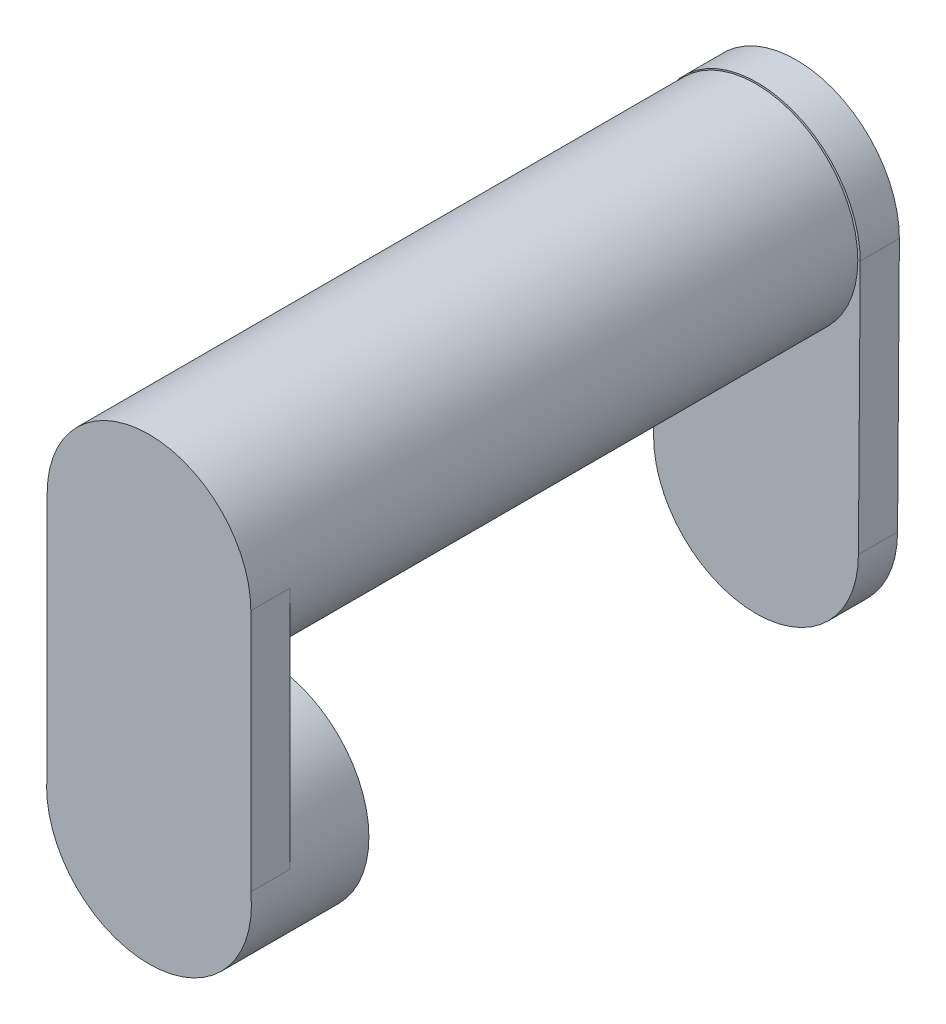
SolidWorks part; units mm, degrees
material "Ti-6Al-2Sn-2Zr-2Mo-2Cr-0.25Si (SS)"
ref_plane "Front Plane" through (0, 0, 0) normal (0, 0, 1) x (1, 0, 0)
ref_plane "Top Plane" through (0, 0, 0) normal (0, 1, 0) x (1, 0, 0)
ref_plane "Right Plane" through (0, 0, 0) normal (1, 0, 0) x (0, 0, -1)
sketch "Sketch1" plane through (0, 0, 0) normal (0, 0, 1) x (1, 0, 0)
  circle A0 centre (0, 0) radius 26.15
  circle A1 centre (0, 0) radius 20.4
  dimension "D1" = 52.3
  dimension "D2" = 40.8
extrude "Boss-Extrude1" add sketch "Sketch1" along normal blind 30 contours A1 | A0
ref_plane "Plane1" through (0, 0, 30) normal (0, 0, 1) x (1, 0, 0)
sketch "Sketch2" plane through (0, 0, 30) normal (0, 0, 1) x (1, 0, 0)
  circle A0 centre (0, 0) radius 26.15
sketch "Sketch10" plane through (0, 0, 30) normal (0, 0, 1) x (1, 0, 0)
  line L0 (-26, 65) -> (-26, 0)
  line L1 (26, 65) -> (26, 0)
  arc A0 (-26, 0) -> (26, 0) centre (0, 0) ccw
  arc A1 (26, 65) -> (-26, 65) centre (0, 65) ccw
  dimension "D1" = 52
  dimension "D2" = 65
extrude "Boss-Extrude7" add sketch "Sketch10" against normal blind 10
ref_plane "Plane5" through (0, 0, 20) normal (0, 0, -1) x (-1, 0, 0)
sketch "Sketch11" plane through (0, 0, 20) normal (0, 0, -1) x (-1, 0, 0)
  circle A0 centre (0, 65) radius 26
extrude "Extrude-Thin1" add sketch "Sketch11" along normal blind 145 thin contours A0 thin type one direction reverse wall 8
ref_plane "Plane6" through (0, 0, -125) normal (0, 0, -1) x (-1, 0, 0)
sketch "Sketch12" plane through (0, 0, -125) normal (0, 0, -1) x (-1, 0, 0)
  line L0 (-26.6135, 65.1347) -> (-26.15, 0)
  line L1 (26, 65) -> (26.15, 0)
  arc A0 (26.0024, 63.9396) -> (-26.6108, 64.7602) centre (-0.2919, 65.1347) ccw
  arc A1 (-26.15, 0) -> (26.1497, 0.1207) centre (0, 0) ccw
extrude "Boss-Extrude8" add sketch "Sketch12" along normal blind 10 contours L0 A1 L1 A0 region at (0.1509, 32.7122, -125)
